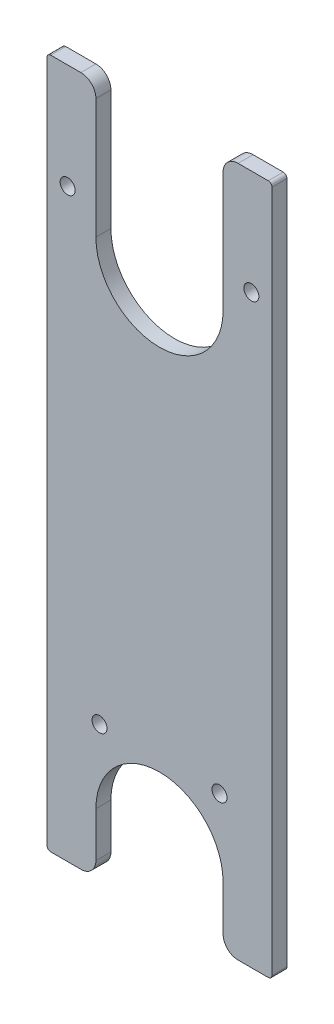
SolidWorks part; units mm, degrees
material "PC High Viscosity"
ref_plane "Front Plane" through (0, 0, 0) normal (0, 0, 1) x (1, 0, 0)
ref_plane "Top Plane" through (0, 0, 0) normal (0, 1, 0) x (1, 0, 0)
ref_plane "Right Plane" through (0, 0, 0) normal (1, 0, 0) x (0, 0, -1)
sketch "Sketch2" plane through (0, 0, 0) normal (0, 0, 1) x (1, 0, 0)
  line L0 (-47.625, -279.4) -> (-26.924, -279.4)
  line L1 (-26.924, -279.4) -> (-26.924, -254)
  line L2 (-47.625, -279.4) -> (-47.625, 12.7)
  line L3 (-47.625, 12.7) -> (-26.924, 12.7)
  line L4 (-26.924, 12.7) -> (-26.924, -44.45)
  line L5 (0, 0) -> (0, -254) construction
  line L6 (47.625, 12.7) -> (26.924, 12.7)
  line L7 (26.924, -279.4) -> (26.924, -254)
  line L8 (47.625, -279.4) -> (26.924, -279.4)
  line L9 (26.924, 12.7) -> (26.924, -44.45)
  line L10 (47.625, -279.4) -> (47.625, 12.7)
  circle A0 centre (0, 0) radius 25.4 construction
  circle A1 centre (0, -254) radius 25.4 construction
  arc A2 (-26.924, -254) -> (26.924, -254) centre (0, -254) cw
  arc A3 (-26.924, -44.45) -> (26.924, -44.45) centre (0, -44.45) ccw
  point P3 (-47.625, 11.676)
  dimension "D2" = 50.8
  dimension "D3" = 26.924
  dimension "D1" = 254
  dimension "D4" = 22.225
  dimension "D5" = 44.45
  dimension "D6" = 12.7
extrude "Boss-Extrude1" add sketch "Sketch2" along normal blind 6.35
fillet "Fillet1" radius 6.35 4 edges at (26.924, -279.4, 3.175) (-26.924, -279.4, 3.175) (26.924, 12.7, 3.175) (-26.924, 12.7, 3.175)
fillet "Fillet2" radius 1.5875 4 edges at (-47.625, 12.7, 3.175) (47.625, 12.7, 3.175) (47.625, -279.4, 3.175) (-47.625, -279.4, 3.175)
hole_wizard "1/4 (0.25) Diameter Hole1" positions "Sketch4" profile "Sketch5" hole size "1/4" standard "ANSI Inch" end condition through all
sketch "Sketch4" plane through (0, 0, 6.35) normal (0, 0, 1) x (1, 0, 0)
  line L0 (0, 0) -> (0, -227.076) construction
  line L1 (-46.0375, -279.4) -> (-33.274, -279.4) construction
  arc A0 (26.924, -254) -> (-26.924, -254) centre (0, -254) ccw construction
  point P0 (-25.4, -222.25)
  point P2 (-38.8938, -31.75)
  point P12 (38.8938, -31.75)
  point P13 (25.4, -222.25)
  point P16 (-31.1546, -222.25)
  dimension "D1" = 77.7875
  dimension "D2" = 57.15
  dimension "D3" = 247.65
  dimension "D4" = 50.8
sketch "Sketch5" plane through (-25.4, -222.25, 6.35) normal (1, 0, 0) x (0, -1, 0)
  line L0 (0, 0) -> (0, 6.35)
  line L1 (0, 6.35) -> (3.175, 6.35)
  line L2 (3.175, 6.35) -> (3.175, 0)
  line L5 (3.175, 0) -> (0, 0)
  line L11 (0, -6.35) -> (0, 107.95) construction
  dimension "Thru Hole Dia." = 6.35
  dimension "Thru Hole Depth" = 6.35
